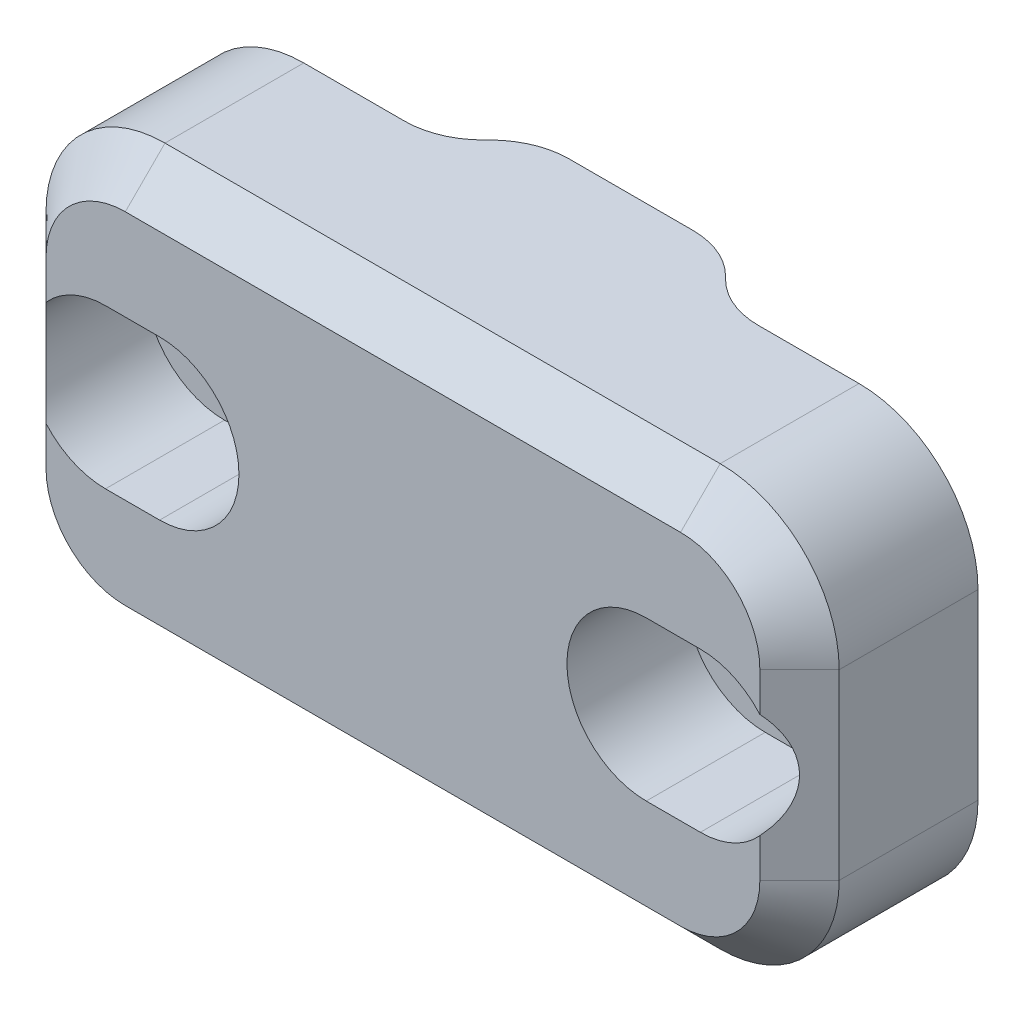
SolidWorks part; units mm, degrees
ref_plane "Front Plane" through (0, 0, 0) normal (0, 0, 1) x (1, 0, 0)
ref_plane "Top Plane" through (0, 0, 0) normal (0, 1, 0) x (1, 0, 0)
ref_plane "Right Plane" through (0, 0, 0) normal (1, 0, 0) x (0, 0, -1)
sketch "Sketch1" plane through (0, 0, 0) normal (0, 0, 1) x (1, 0, 0)
  line L0 (-11.25, 84) -> (-11.25, 79.4) construction
  line L1 (8.75, 74.4) -> (-11.25, 74.4)
  line L2 (8.75, 74.4) -> (8.75, 87)
  line L3 (8.75, 87) -> (-11.25, 87)
  line L4 (-11.25, 74.4) -> (-11.25, 87)
  line L5 (8.75, 74.4) -> (-11.25, 87) construction
  line L6 (8.75, 87) -> (-11.25, 74.4) construction
  line L7 (5.75, 87) -> (-8.25, 87) construction
  point P4 (-1.25, 80.7)
extrude "Boss-Extrude1" add sketch "Sketch1" along normal up to surface (5 mm away)
sketch "Sketch2" plane through (0, 87, 0) normal (0, 1, 0) x (1, 0, 0)
  line L0 (-11.25, -5) -> (-11.25, 0) construction
  line L1 (8.75, 0) -> (-11.25, 0)
  line L2 (8.75, 0) -> (8.75, -0.5)
  line L3 (8.75, -0.5) -> (-11.25, -0.5)
  line L4 (-11.25, 0) -> (-11.25, -0.5)
  line L5 (8.75, 0) -> (-11.25, -0.5) construction
  line L6 (8.75, -0.5) -> (-11.25, 0) construction
  point P4 (-1.25, -0.25)
  dimension "D1" = 0.5
extrude "Cut-Extrude1" cut sketch "Sketch2" against normal up to next
sketch "Sketch3" plane through (0, 0, 5) normal (0, 0, 1) x (1, 0, 0)
  line L0 (8.75, 74.4) -> (8.75, 87) construction
  line L1 (-11.25, 74.4) -> (8.75, 74.4)
  line L2 (-11.25, 74.4) -> (-11.25, 76.4)
  line L3 (-11.25, 76.4) -> (8.75, 76.4)
  line L4 (8.75, 74.4) -> (8.75, 76.4)
  line L5 (-11.25, 74.4) -> (8.75, 76.4) construction
  line L6 (-11.25, 76.4) -> (8.75, 74.4) construction
  point P4 (-1.25, 75.4)
  dimension "D1" = 2
extrude "Cut-Extrude2" cut sketch "Sketch3" against normal up to next
sketch "Sketch4" plane through (0, 87, 0) normal (0, 1, 0) x (1, 0, 0)
  line L0 (-4.8848, -0.5) -> (-3.6348, 0.75)
  line L1 (-11.25, -0.5) -> (8.75, -0.5) construction
  line L2 (-3.6348, 0.75) -> (1.1348, 0.75)
  line L3 (1.1348, 0.75) -> (2.3848, -0.5)
  line L4 (-4.8848, -0.5) -> (2.3848, -0.5)
  circle A0 centre (-1.25, 0) radius 2.5 construction
  point P9 (-1.25, 0.75)
  dimension "D1" = 5
  dimension "D2" = 1.25
  dimension "D3" = 45
extrude "Boss-Extrude2" add sketch "Sketch4" against normal up to surface (10.6 mm away) up to face at (-1.25, 76.4, 2.75)
sketch "Sketch5" plane through (0, 87, 0) normal (0, 1, 0) x (1, 0, 0)
  line L0 (8.75, -5) -> (-11.25, -5) construction
  point P0 (-1.25, -5)
ref_plane "Plane1" through (-1.25, 0, 0) normal (1, 0, 0) x (0, 0, -1)
sketch "Sketch6" plane through (0, 0, 0.5) normal (0, 0, -1) x (-1, 0, 0)
  line L0 (-5.5674, 87) -> (-5.5674, 76.4) construction
  line L1 (-2.3848, 87) -> (-8.75, 87) construction
  line L2 (-2.3848, 76.4) -> (-8.75, 76.4) construction
  line L3 (-6.3174, 81.7) -> (-4.8174, 81.7) construction
  line L4 (-6.3174, 82.75) -> (-4.8174, 82.75)
  line L5 (-6.3174, 80.65) -> (-4.8174, 80.65)
  circle A0 centre (-5.5674, 81.7) radius 1.05 construction
  arc A1 (-6.3174, 82.75) -> (-6.3174, 80.65) centre (-6.3174, 81.7) ccw
  arc A2 (-4.8174, 80.65) -> (-4.8174, 82.75) centre (-4.8174, 81.7) ccw
  point P10 (-5.5674, 81.7)
  dimension "D1" = 2.1
  dimension "D2" = 1.5
extrude "Cut-Extrude4" cut sketch "Sketch6" against normal through all both and the other way through all
fillet "Fillet1" radius 3 4 edges at (8.75, 76.4, 2.75) (-11.25, 76.4, 2.75) (-11.25, 87, 2.75) (8.75, 87, 2.75)
sketch "Sketch7" plane through (0, 0, 5) normal (0, 0, 1) x (1, 0, 0)
  line L0 (6.25, 81.7) -> (4.8848, 81.7) construction
  line L1 (6.25, 79.7) -> (4.8848, 79.7)
  line L2 (6.25, 83.7) -> (4.8848, 83.7)
  line L4 (8.75, 79.4) -> (8.75, 84) construction
  circle A0 centre (5.5674, 81.7) radius 2 construction
  circle A2 centre (5.5674, 81.7) radius 1.05 construction
  arc A3 (6.25, 79.7) -> (6.25, 83.7) centre (6.25, 81.7) ccw
  arc A4 (4.8848, 83.7) -> (4.8848, 79.7) centre (4.8848, 81.7) ccw
  point P6 (5.5674, 81.7)
  point P13 (8.25, 81.7)
  dimension "D1" = 4
  dimension "D2" = 0.5
extrude "Cut-Extrude5" cut sketch "Sketch7" against normal blind 3
mirror "Mirror1" about plane through (-1.25, 0, 0) normal (1, 0, 0) of "Cut-Extrude4", "Cut-Extrude5"
chamfer "Chamfer2" distance 1 angle 45 8 edges at (8.75, 81.7, 5) (7.8713, 86.1213, 5) (7.8713, 77.2787, 5) (-1.25, 87, 5) (-1.25, 76.4, 5) (-10.3713, 86.1213, 5) (-10.3713, 77.2787, 5) (-11.25, 81.7, 5)
fillet "Fillet2" radius 2 4 edges at (2.3848, 81.7, 0.5) (-4.8848, 81.7, 0.5) (1.1348, 81.7, -0.75) (-3.6348, 81.7, -0.75)
